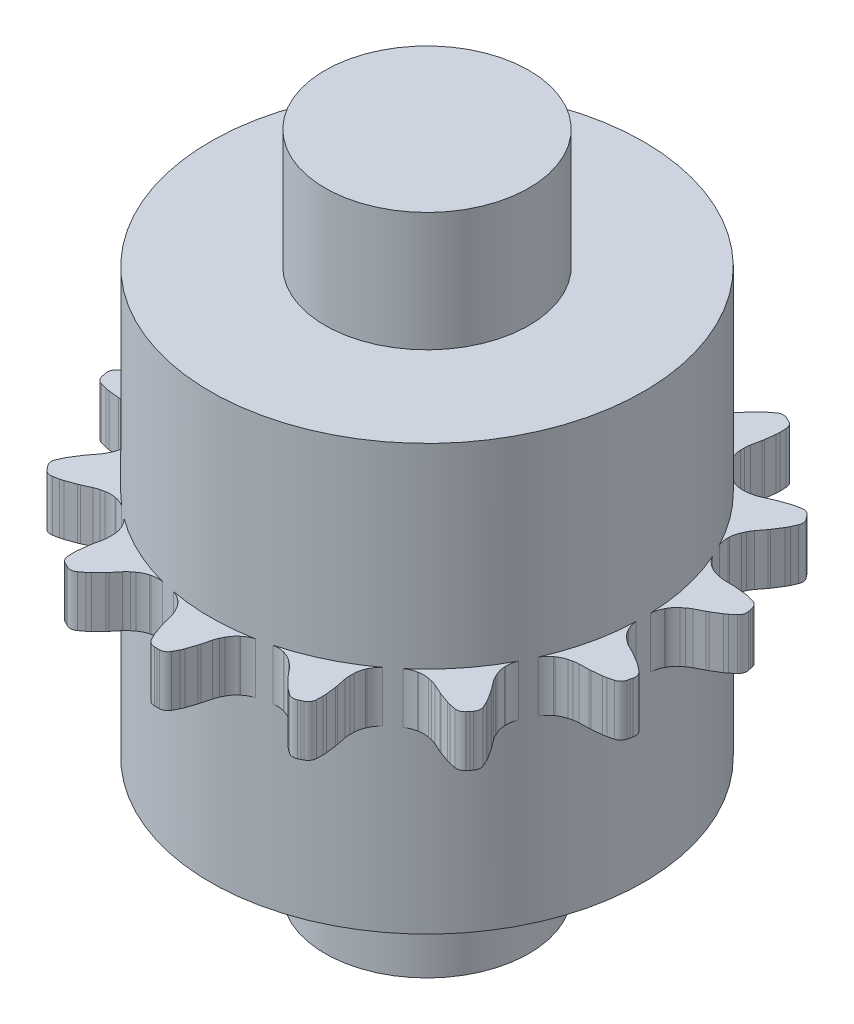
SolidWorks part; units mm, degrees
ref_plane "Front Plane" through (0, 0, 0) normal (0, 0, 1) x (1, 0, 0)
ref_plane "Top Plane" through (0, 0, 0) normal (0, 1, 0) x (1, 0, 0)
ref_plane "Right Plane" through (0, 0, 0) normal (1, 0, 0) x (0, 0, -1)
ref_axis "RotationAxis_J1_Radiator" through (0, 0, 0) along (0, 1, 0)
ref_plane "ContactPlane_J1_Bearing_Radiator" through (0, 0, 0) normal (0, 1, 0) x (1, 0, 0)
sketch "Sketch1" plane through (0, 0, 0) normal (0, 0, 1) x (1, 0, 0)
  line L0 (12.74, 25) -> (12.74, 0)
  line L1 (55, 0) -> (-55, 0) construction
  line L2 (12.74, 0) -> (6, 0)
  line L3 (6, 0) -> (6, -7)
  line L4 (6, -7) -> (0, -7)
  line L5 (0, -7) -> (0, 32)
  line L6 (0, 32) -> (6, 32)
  line L7 (6, 32) -> (6, 25)
  line L8 (6, 25) -> (12.74, 25)
  line L10 (0, 0) -> (0, 69.0457) construction
  point P14 (3, 32)
  dimension "D1" = 6
  dimension "D2" = 12.74
  dimension "D3" = 7
  dimension "D4" = 7
  dimension "D6" = 25
revolve "Revolve1" add sketch "Sketch1" angle 360 about axis through (0, 0, 0) along (0, 1, 0)
ref_plane "ContactPlane_J1_Radiator_Bearing" through (0, 25, 0) normal (0, 1, 0) x (1, 0, 0)
ref_plane "GearDefinitionPlane" through (0, 10.5, 0) normal (0, -1, 0) x (-1, 0, 0)
sketch "Sketch2" plane through (0, 10.5, 0) normal (0, -1, 0) x (-1, 0, 0)
sketch "Sketch3" plane through (0, 10.5, 0) normal (0, -1, 0) x (-1, 0, 0)
  line L0 (-2.86, 12.4148) -> (2.86, 12.4148)
  line L1 (0, 12.74) -> (0, 18.3584) construction
  line L2 (-2.86, 12.4148) -> (-2.5337, 12.4802)
  line L3 (-1.8465, 12.8171) -> (-1.7975, 12.8596)
  line L4 (-1.4378, 13.3226) -> (-1.333, 13.5324)
  line L5 (-1.2199, 13.8374) -> (-1.0814, 14.3883)
  line L6 (-1.0472, 14.5043) -> (-0.8487, 15.0895)
  line L7 (-0.7604, 15.2972) -> (-0.5938, 15.6191)
  line L8 (-0.1482, 15.8893) -> (0, 15.8888)
  line L9 (2.86, 12.4148) -> (2.5337, 12.4802)
  line L10 (1.8465, 12.8171) -> (1.7975, 12.8596)
  line L11 (0.1482, 15.8893) -> (0, 15.8888)
  line L12 (0.7604, 15.2972) -> (0.5938, 15.6191)
  line L13 (1.0472, 14.5043) -> (0.8487, 15.0895)
  line L14 (1.2199, 13.8374) -> (1.0814, 14.3883)
  line L15 (1.4378, 13.3226) -> (1.333, 13.5324)
  line L16 (2.8098, 12.4263) -> (3.1321, 12.3436)
  line L17 (3.8975, 12.349) -> (3.9601, 12.366)
  line L18 (4.485, 12.6271) -> (4.6705, 12.7706)
  line L19 (4.9047, 12.9964) -> (5.2686, 13.4326)
  line L20 (7.9634, 9.9445) -> (7.6978, 10.1449)
  line L21 (7.2248, 10.7466) -> (7.199, 10.8062)
  line L22 (7.0759, 11.3794) -> (7.0724, 11.6139)
  line L23 (7.1029, 11.9378) -> (7.2172, 12.4942)
  line L24 (7.2367, 12.6136) -> (7.3118, 13.2269)
  line L25 (7.3223, 13.4524) -> (7.3118, 13.8147)
  line L26 (7.0276, 14.2514) -> (6.8939, 14.3153)
  line L27 (6.7606, 14.38) -> (6.8939, 14.3153)
  line L28 (5.9521, 14.1122) -> (6.2419, 14.3299)
  line L29 (5.3497, 13.5223) -> (5.7824, 13.9634)
  line L30 (2.8098, 12.4263) -> (7.9634, 9.9445)
  line L31 (7.9231, 9.9766) -> (8.1777, 9.7623)
  line L32 (8.8695, 9.435) -> (8.9333, 9.4231)
  line L33 (9.5196, 9.4307) -> (9.7489, 9.4795)
  line L34 (10.0579, 9.5812) -> (10.575, 9.8164)
  line L35 (11.4895, 5.5045) -> (11.3372, 5.8003)
  line L36 (11.1721, 6.5477) -> (11.1747, 6.6125)
  line L37 (11.3125, 7.1824) -> (11.4111, 7.3951)
  line L38 (11.5791, 7.6737) -> (11.9235, 8.1255)
  line L39 (11.9929, 8.2246) -> (12.3266, 8.7446)
  line L40 (12.4339, 8.9432) -> (12.5817, 9.2741)
  line L41 (12.5151, 9.7909) -> (12.4224, 9.9065)
  line L42 (12.3303, 10.0227) -> (12.4224, 9.9065)
  line L43 (11.4858, 10.1321) -> (11.8413, 10.2026)
  line L44 (10.687, 9.862) -> (11.2683, 10.0717)
  line L45 (7.9231, 9.9766) -> (11.4895, 5.5045)
  line L46 (11.4672, 5.5509) -> (11.6035, 5.2473)
  line L47 (12.0849, 4.6523) -> (12.1372, 4.6139)
  line L48 (12.6687, 4.3664) -> (12.8965, 4.3108)
  line L49 (13.219, 4.2684) -> (13.7869, 4.256)
  line L50 (12.74, -0.0257) -> (12.7311, 0.3069)
  line L51 (12.9067, 1.0518) -> (12.9372, 1.1091)
  line L52 (13.3086, 1.5628) -> (13.4897, 1.7117)
  line L53 (13.7619, 1.8898) -> (14.2682, 2.1474)
  line L54 (14.3737, 2.2066) -> (14.9, 2.5303)
  line L55 (15.0829, 2.6626) -> (15.3596, 2.8967)
  line L56 (15.5239, 3.3912) -> (15.4904, 3.5356)
  line L57 (15.4579, 3.6802) -> (15.4904, 3.5356)
  line L58 (14.7445, 4.1453) -> (15.0954, 4.0545)
  line L59 (13.9076, 4.2485) -> (14.5223, 4.1852)
  line L60 (11.4672, 5.5509) -> (12.74, -0.0257)
  line L61 (12.74, 0.0257) -> (12.7311, -0.3069)
  line L62 (12.9067, -1.0518) -> (12.9372, -1.1091)
  line L63 (13.3086, -1.5628) -> (13.4897, -1.7117)
  line L64 (13.7619, -1.8898) -> (14.2682, -2.1474)
  line L65 (11.4672, -5.5509) -> (11.6035, -5.2473)
  line L66 (12.0849, -4.6523) -> (12.1372, -4.6139)
  line L67 (12.6687, -4.3664) -> (12.8965, -4.3108)
  line L68 (13.219, -4.2684) -> (13.7869, -4.256)
  line L69 (13.9076, -4.2485) -> (14.5223, -4.1852)
  line L70 (14.7445, -4.1453) -> (15.0954, -4.0545)
  line L71 (15.4579, -3.6802) -> (15.4904, -3.5356)
  line L72 (15.5239, -3.3912) -> (15.4904, -3.5356)
  line L73 (15.0829, -2.6626) -> (15.3596, -2.8967)
  line L74 (14.3737, -2.2066) -> (14.9, -2.5303)
  line L75 (12.74, 0.0257) -> (11.4672, -5.5509)
  line L76 (11.4895, -5.5045) -> (11.3372, -5.8003)
  line L77 (11.1721, -6.5477) -> (11.1747, -6.6125)
  line L78 (11.3125, -7.1824) -> (11.4111, -7.3951)
  line L79 (11.5791, -7.6737) -> (11.9235, -8.1255)
  line L80 (7.9231, -9.9766) -> (8.1777, -9.7623)
  line L81 (8.8695, -9.435) -> (8.9333, -9.4231)
  line L82 (9.5196, -9.4307) -> (9.7489, -9.4795)
  line L83 (10.0579, -9.5812) -> (10.575, -9.8164)
  line L84 (10.687, -9.862) -> (11.2683, -10.0717)
  line L85 (11.4858, -10.1321) -> (11.8413, -10.2026)
  line L86 (12.3303, -10.0227) -> (12.4224, -9.9065)
  line L87 (12.5151, -9.7909) -> (12.4224, -9.9065)
  line L88 (12.4339, -8.9432) -> (12.5817, -9.2741)
  line L89 (11.9929, -8.2246) -> (12.3266, -8.7446)
  line L90 (11.4895, -5.5045) -> (7.9231, -9.9766)
  line L91 (7.9634, -9.9445) -> (7.6978, -10.1449)
  line L92 (7.2248, -10.7466) -> (7.199, -10.8062)
  line L93 (7.0759, -11.3794) -> (7.0724, -11.6139)
  line L94 (7.1029, -11.9378) -> (7.2172, -12.4942)
  line L95 (2.8098, -12.4263) -> (3.1321, -12.3436)
  line L96 (3.8975, -12.349) -> (3.9601, -12.366)
  line L97 (4.485, -12.6271) -> (4.6705, -12.7706)
  line L98 (4.9047, -12.9964) -> (5.2686, -13.4326)
  line L99 (5.3497, -13.5223) -> (5.7824, -13.9634)
  line L100 (5.9521, -14.1122) -> (6.2419, -14.3299)
  line L101 (6.7606, -14.38) -> (6.8939, -14.3153)
  line L102 (7.0276, -14.2514) -> (6.8939, -14.3153)
  line L103 (7.3223, -13.4524) -> (7.3118, -13.8147)
  line L104 (7.2367, -12.6136) -> (7.3118, -13.2269)
  line L105 (7.9634, -9.9445) -> (2.8098, -12.4263)
  line L106 (2.86, -12.4148) -> (2.5337, -12.4802)
  line L107 (1.8465, -12.8171) -> (1.7975, -12.8596)
  line L108 (1.4378, -13.3226) -> (1.333, -13.5324)
  line L109 (1.2199, -13.8374) -> (1.0814, -14.3883)
  line L110 (-2.86, -12.4148) -> (-2.5337, -12.4802)
  line L111 (-1.8465, -12.8171) -> (-1.7975, -12.8596)
  line L112 (-1.4378, -13.3226) -> (-1.333, -13.5324)
  line L113 (-1.2199, -13.8374) -> (-1.0814, -14.3883)
  line L114 (-1.0472, -14.5043) -> (-0.8487, -15.0895)
  line L115 (-0.7604, -15.2972) -> (-0.5938, -15.6191)
  line L116 (-0.1482, -15.8893) -> (0, -15.8888)
  line L117 (0.1482, -15.8893) -> (0, -15.8888)
  line L118 (0.7604, -15.2972) -> (0.5938, -15.6191)
  line L119 (1.0472, -14.5043) -> (0.8487, -15.0895)
  line L120 (2.86, -12.4148) -> (-2.86, -12.4148)
  line L121 (-2.8098, -12.4263) -> (-3.1321, -12.3436)
  line L122 (-3.8975, -12.349) -> (-3.9601, -12.366)
  line L123 (-4.485, -12.6271) -> (-4.6705, -12.7706)
  line L124 (-4.9047, -12.9964) -> (-5.2686, -13.4326)
  line L125 (-7.9634, -9.9445) -> (-7.6978, -10.1449)
  line L126 (-7.2248, -10.7466) -> (-7.199, -10.8062)
  line L127 (-7.0759, -11.3794) -> (-7.0724, -11.6139)
  line L128 (-7.1029, -11.9378) -> (-7.2172, -12.4942)
  line L129 (-7.2367, -12.6136) -> (-7.3118, -13.2269)
  line L130 (-7.3223, -13.4524) -> (-7.3118, -13.8147)
  line L131 (-7.0276, -14.2514) -> (-6.8939, -14.3153)
  line L132 (-6.7606, -14.38) -> (-6.8939, -14.3153)
  line L133 (-5.9521, -14.1122) -> (-6.2419, -14.3299)
  line L134 (-5.3497, -13.5223) -> (-5.7824, -13.9634)
  line L135 (-2.8098, -12.4263) -> (-7.9634, -9.9445)
  line L136 (-7.9231, -9.9766) -> (-8.1777, -9.7623)
  line L137 (-8.8695, -9.435) -> (-8.9333, -9.4231)
  line L138 (-9.5196, -9.4307) -> (-9.7489, -9.4795)
  line L139 (-10.0579, -9.5812) -> (-10.575, -9.8164)
  line L140 (-11.4895, -5.5045) -> (-11.3372, -5.8003)
  line L141 (-11.1721, -6.5477) -> (-11.1747, -6.6125)
  line L142 (-11.3125, -7.1824) -> (-11.4111, -7.3951)
  line L143 (-11.5791, -7.6737) -> (-11.9235, -8.1255)
  line L144 (-11.9929, -8.2246) -> (-12.3266, -8.7446)
  line L145 (-12.4339, -8.9432) -> (-12.5817, -9.2741)
  line L146 (-12.5151, -9.7909) -> (-12.4224, -9.9065)
  line L147 (-12.3303, -10.0227) -> (-12.4224, -9.9065)
  line L148 (-11.4858, -10.1321) -> (-11.8413, -10.2026)
  line L149 (-10.687, -9.862) -> (-11.2683, -10.0717)
  line L150 (-7.9231, -9.9766) -> (-11.4895, -5.5045)
  line L151 (-11.4672, -5.5509) -> (-11.6035, -5.2473)
  line L152 (-12.0849, -4.6523) -> (-12.1372, -4.6139)
  line L153 (-12.6687, -4.3664) -> (-12.8965, -4.3108)
  line L154 (-13.219, -4.2684) -> (-13.7869, -4.256)
  line L155 (-12.74, 0.0257) -> (-12.7311, -0.3069)
  line L156 (-12.9067, -1.0518) -> (-12.9372, -1.1091)
  line L157 (-13.3086, -1.5628) -> (-13.4897, -1.7117)
  line L158 (-13.7619, -1.8898) -> (-14.2682, -2.1474)
  line L159 (-14.3737, -2.2066) -> (-14.9, -2.5303)
  line L160 (-15.0829, -2.6626) -> (-15.3596, -2.8967)
  line L161 (-15.5239, -3.3912) -> (-15.4904, -3.5356)
  line L162 (-15.4579, -3.6802) -> (-15.4904, -3.5356)
  line L163 (-14.7445, -4.1453) -> (-15.0954, -4.0545)
  line L164 (-13.9076, -4.2485) -> (-14.5223, -4.1852)
  line L165 (-11.4672, -5.5509) -> (-12.74, 0.0257)
  line L166 (-12.74, -0.0257) -> (-12.7311, 0.3069)
  line L167 (-12.9067, 1.0518) -> (-12.9372, 1.1091)
  line L168 (-13.3086, 1.5628) -> (-13.4897, 1.7117)
  line L169 (-13.7619, 1.8898) -> (-14.2682, 2.1474)
  line L170 (-11.4672, 5.5509) -> (-11.6035, 5.2473)
  line L171 (-12.0849, 4.6523) -> (-12.1372, 4.6139)
  line L172 (-12.6687, 4.3664) -> (-12.8965, 4.3108)
  line L173 (-13.219, 4.2684) -> (-13.7869, 4.256)
  line L174 (-13.9076, 4.2485) -> (-14.5223, 4.1852)
  line L175 (-14.7445, 4.1453) -> (-15.0954, 4.0545)
  line L176 (-15.4579, 3.6802) -> (-15.4904, 3.5356)
  line L177 (-15.5239, 3.3912) -> (-15.4904, 3.5356)
  line L178 (-15.0829, 2.6626) -> (-15.3596, 2.8967)
  line L179 (-14.3737, 2.2066) -> (-14.9, 2.5303)
  line L180 (-12.74, -0.0257) -> (-11.4672, 5.5509)
  line L181 (-11.4895, 5.5045) -> (-11.3372, 5.8003)
  line L182 (-11.1721, 6.5477) -> (-11.1747, 6.6125)
  line L183 (-11.3125, 7.1824) -> (-11.4111, 7.3951)
  line L184 (-11.5791, 7.6737) -> (-11.9235, 8.1255)
  line L185 (-7.9231, 9.9766) -> (-8.1777, 9.7623)
  line L186 (-8.8695, 9.435) -> (-8.9333, 9.4231)
  line L187 (-9.5196, 9.4307) -> (-9.7489, 9.4795)
  line L188 (-10.0579, 9.5812) -> (-10.575, 9.8164)
  line L189 (-10.687, 9.862) -> (-11.2683, 10.0717)
  line L190 (-11.4858, 10.1321) -> (-11.8413, 10.2026)
  line L191 (-12.3303, 10.0227) -> (-12.4224, 9.9065)
  line L192 (-12.5151, 9.7909) -> (-12.4224, 9.9065)
  line L193 (-12.4339, 8.9432) -> (-12.5817, 9.2741)
  line L194 (-11.9929, 8.2246) -> (-12.3266, 8.7446)
  line L195 (-11.4895, 5.5045) -> (-7.9231, 9.9766)
  line L196 (-7.9634, 9.9445) -> (-7.6978, 10.1449)
  line L197 (-7.2248, 10.7466) -> (-7.199, 10.8062)
  line L198 (-7.0759, 11.3794) -> (-7.0724, 11.6139)
  line L199 (-7.1029, 11.9378) -> (-7.2172, 12.4942)
  line L200 (-2.8098, 12.4263) -> (-3.1321, 12.3436)
  line L201 (-3.8975, 12.349) -> (-3.9601, 12.366)
  line L202 (-4.485, 12.6271) -> (-4.6705, 12.7706)
  line L203 (-4.9047, 12.9964) -> (-5.2686, 13.4326)
  line L204 (-5.3497, 13.5223) -> (-5.7824, 13.9634)
  line L205 (-5.9521, 14.1122) -> (-6.2419, 14.3299)
  line L206 (-6.7606, 14.38) -> (-6.8939, 14.3153)
  line L207 (-7.0276, 14.2514) -> (-6.8939, 14.3153)
  line L208 (-7.3223, 13.4524) -> (-7.3118, 13.8147)
  line L209 (-7.2367, 12.6136) -> (-7.3118, 13.2269)
  line L210 (-7.9634, 9.9445) -> (-2.8098, 12.4263)
  circle A0 centre (0, 0) radius 12.74 construction
  circle A1 centre (0, 0) radius 12.74
  arc A2 (-2.5337, 12.4802) -> (-1.8465, 12.8171) centre (-2.8285, 13.951) ccw
  arc A3 (-0.8487, 15.0895) -> (-0.7604, 15.2972) centre (0.5718, 14.6077) cw
  arc A4 (-1.0814, 14.3883) -> (-1.0472, 14.5043) centre (0.3733, 14.0226) cw
  arc A5 (-1.333, 13.5324) -> (-1.2199, 13.8374) centre (-2.6746, 14.2032) ccw
  arc A6 (-1.7975, 12.8596) -> (-1.4378, 13.3226) centre (-2.7795, 13.9935) ccw
  arc A7 (-0.5938, 15.6191) -> (-0.1482, 15.8893) centre (-0.1497, 15.3893) cw
  arc A8 (2.5337, 12.4802) -> (1.8465, 12.8171) centre (2.8285, 13.951) cw
  arc A9 (1.7975, 12.8596) -> (1.4378, 13.3226) centre (2.7795, 13.9935) cw
  arc A10 (0.5938, 15.6191) -> (0.1482, 15.8893) centre (0.1497, 15.3893) ccw
  arc A11 (1.333, 13.5324) -> (1.2199, 13.8374) centre (2.6746, 14.2032) cw
  arc A12 (1.0814, 14.3883) -> (1.0472, 14.5043) centre (-0.3733, 14.0226) ccw
  arc A13 (0.8487, 15.0895) -> (0.7604, 15.2972) centre (-0.5718, 14.6077) ccw
  arc A14 (3.1321, 12.3436) -> (3.8975, 12.349) centre (3.5047, 13.7967) ccw
  arc A15 (3.9601, 12.366) -> (4.485, 12.6271) centre (3.5673, 13.8136) ccw
  arc A16 (4.6705, 12.7706) -> (4.9047, 12.9964) centre (3.7528, 13.9571) ccw
  arc A17 (5.2686, 13.4326) -> (5.3497, 13.5223) centre (6.4205, 12.4719) cw
  arc A18 (7.6978, 10.1449) -> (7.2248, 10.7466) centre (8.6015, 11.3421) cw
  arc A19 (7.199, 10.8062) -> (7.0759, 11.3794) centre (8.5758, 11.4017) cw
  arc A20 (7.0724, 11.6139) -> (7.1029, 11.9378) centre (8.5723, 11.6361) cw
  arc A21 (7.2172, 12.4942) -> (7.2367, 12.6136) centre (5.7478, 12.7959) ccw
  arc A22 (7.3118, 13.2269) -> (7.3223, 13.4524) centre (5.8229, 13.4092) ccw
  arc A23 (7.3118, 13.8147) -> (7.0276, 14.2514) centre (6.8121, 13.8003) ccw
  arc A24 (6.2419, 14.3299) -> (6.7606, 14.38) centre (6.5422, 13.9302) cw
  arc A25 (5.7824, 13.9634) -> (5.9521, 14.1122) centre (6.8532, 12.913) cw
  arc A26 (8.1777, 9.7623) -> (8.8695, 9.435) centre (9.1437, 10.9097) ccw
  arc A27 (8.9333, 9.4231) -> (9.5196, 9.4307) centre (9.2076, 10.8979) ccw
  arc A28 (9.7489, 9.4795) -> (10.0579, 9.5812) centre (9.4369, 10.9466) ccw
  arc A29 (10.575, 9.8164) -> (10.687, 9.862) centre (11.1961, 8.451) cw
  arc A30 (11.3372, 5.8003) -> (11.1721, 6.5477) centre (12.6709, 6.4868) cw
  arc A31 (11.1747, 6.6125) -> (11.3125, 7.1824) centre (12.6735, 6.5517) cw
  arc A32 (11.4111, 7.3951) -> (11.5791, 7.6737) centre (12.7721, 6.7644) cw
  arc A33 (11.9235, 8.1255) -> (11.9929, 8.2246) centre (10.7305, 9.0348) ccw
  arc A34 (12.3266, 8.7446) -> (12.4339, 8.9432) centre (11.0643, 9.5548) ccw
  arc A35 (12.5817, 9.2741) -> (12.5151, 9.7909) centre (12.1252, 9.478) ccw
  arc A36 (11.8413, 10.2026) -> (12.3303, 10.0227) centre (11.9385, 9.7121) cw
  arc A37 (11.2683, 10.0717) -> (11.4858, 10.1321) centre (11.7773, 8.6607) cw
  arc A38 (11.6035, 5.2473) -> (12.0849, 4.6523) centre (12.9718, 5.862) ccw
  arc A39 (12.1372, 4.6139) -> (12.6687, 4.3664) centre (13.0241, 5.8236) ccw
  arc A40 (12.8965, 4.3108) -> (13.219, 4.2684) centre (13.2519, 5.7681) ccw
  arc A41 (13.7869, 4.256) -> (13.9076, 4.2485) centre (13.7541, 2.7563) cw
  arc A42 (12.7311, 0.3069) -> (12.9067, 1.0518) centre (14.2306, 0.3468) cw
  arc A43 (12.9372, 1.1091) -> (13.3086, 1.5628) centre (14.2611, 0.404) cw
  arc A44 (13.4897, 1.7117) -> (13.7619, 1.8898) centre (14.4422, 0.5529) cw
  arc A45 (14.2682, 2.1474) -> (14.3737, 2.2066) centre (13.5879, 3.4843) ccw
  arc A46 (14.9, 2.5303) -> (15.0829, 2.6626) centre (14.1143, 3.808) ccw
  arc A47 (15.3596, 2.8967) -> (15.5239, 3.3912) centre (15.0367, 3.2785) ccw
  arc A48 (15.0954, 4.0545) -> (15.4579, 3.6802) centre (14.9701, 3.5704) cw
  arc A49 (14.5223, 4.1852) -> (14.7445, 4.1453) centre (14.3687, 2.6931) cw
  arc A50 (12.7311, -0.3069) -> (12.9067, -1.0518) centre (14.2306, -0.3468) ccw
  arc A51 (12.9372, -1.1091) -> (13.3086, -1.5628) centre (14.2611, -0.404) ccw
  arc A52 (13.4897, -1.7117) -> (13.7619, -1.8898) centre (14.4422, -0.5529) ccw
  arc A53 (14.2682, -2.1474) -> (14.3737, -2.2066) centre (13.5879, -3.4843) cw
  arc A54 (11.6035, -5.2473) -> (12.0849, -4.6523) centre (12.9718, -5.862) cw
  arc A55 (12.1372, -4.6139) -> (12.6687, -4.3664) centre (13.0241, -5.8236) cw
  arc A56 (12.8965, -4.3108) -> (13.219, -4.2684) centre (13.2519, -5.7681) cw
  arc A57 (13.7869, -4.256) -> (13.9076, -4.2485) centre (13.7541, -2.7563) ccw
  arc A58 (14.5223, -4.1852) -> (14.7445, -4.1453) centre (14.3687, -2.6931) ccw
  arc A59 (15.0954, -4.0545) -> (15.4579, -3.6802) centre (14.9701, -3.5704) ccw
  arc A60 (15.3596, -2.8967) -> (15.5239, -3.3912) centre (15.0367, -3.2785) cw
  arc A61 (14.9, -2.5303) -> (15.0829, -2.6626) centre (14.1143, -3.808) cw
  arc A62 (11.3372, -5.8003) -> (11.1721, -6.5477) centre (12.6709, -6.4868) ccw
  arc A63 (11.1747, -6.6125) -> (11.3125, -7.1824) centre (12.6735, -6.5517) ccw
  arc A64 (11.4111, -7.3951) -> (11.5791, -7.6737) centre (12.7721, -6.7644) ccw
  arc A65 (11.9235, -8.1255) -> (11.9929, -8.2246) centre (10.7305, -9.0348) cw
  arc A66 (8.1777, -9.7623) -> (8.8695, -9.435) centre (9.1437, -10.9097) cw
  arc A67 (8.9333, -9.4231) -> (9.5196, -9.4307) centre (9.2076, -10.8979) cw
  arc A68 (9.7489, -9.4795) -> (10.0579, -9.5812) centre (9.4369, -10.9466) cw
  arc A69 (10.575, -9.8164) -> (10.687, -9.862) centre (11.1961, -8.451) ccw
  arc A70 (11.2683, -10.0717) -> (11.4858, -10.1321) centre (11.7773, -8.6607) ccw
  arc A71 (11.8413, -10.2026) -> (12.3303, -10.0227) centre (11.9385, -9.7121) ccw
  arc A72 (12.5817, -9.2741) -> (12.5151, -9.7909) centre (12.1252, -9.478) cw
  arc A73 (12.3266, -8.7446) -> (12.4339, -8.9432) centre (11.0643, -9.5548) cw
  arc A74 (7.6978, -10.1449) -> (7.2248, -10.7466) centre (8.6015, -11.3421) ccw
  arc A75 (7.199, -10.8062) -> (7.0759, -11.3794) centre (8.5758, -11.4017) ccw
  arc A76 (7.0724, -11.6139) -> (7.1029, -11.9378) centre (8.5723, -11.6361) ccw
  arc A77 (7.2172, -12.4942) -> (7.2367, -12.6136) centre (5.7478, -12.7959) cw
  arc A78 (3.1321, -12.3436) -> (3.8975, -12.349) centre (3.5047, -13.7967) cw
  arc A79 (3.9601, -12.366) -> (4.485, -12.6271) centre (3.5673, -13.8136) cw
  arc A80 (4.6705, -12.7706) -> (4.9047, -12.9964) centre (3.7528, -13.9571) cw
  arc A81 (5.2686, -13.4326) -> (5.3497, -13.5223) centre (6.4205, -12.4719) ccw
  arc A82 (5.7824, -13.9634) -> (5.9521, -14.1122) centre (6.8532, -12.913) ccw
  arc A83 (6.2419, -14.3299) -> (6.7606, -14.38) centre (6.5422, -13.9302) ccw
  arc A84 (7.3118, -13.8147) -> (7.0276, -14.2514) centre (6.8121, -13.8003) cw
  arc A85 (7.3118, -13.2269) -> (7.3223, -13.4524) centre (5.8229, -13.4092) cw
  arc A86 (2.5337, -12.4802) -> (1.8465, -12.8171) centre (2.8285, -13.951) ccw
  arc A87 (1.7975, -12.8596) -> (1.4378, -13.3226) centre (2.7795, -13.9935) ccw
  arc A88 (1.333, -13.5324) -> (1.2199, -13.8374) centre (2.6746, -14.2032) ccw
  arc A89 (1.0814, -14.3883) -> (1.0472, -14.5043) centre (-0.3733, -14.0226) cw
  arc A90 (-2.5337, -12.4802) -> (-1.8465, -12.8171) centre (-2.8285, -13.951) cw
  arc A91 (-1.7975, -12.8596) -> (-1.4378, -13.3226) centre (-2.7795, -13.9935) cw
  arc A92 (-1.333, -13.5324) -> (-1.2199, -13.8374) centre (-2.6746, -14.2032) cw
  arc A93 (-1.0814, -14.3883) -> (-1.0472, -14.5043) centre (0.3733, -14.0226) ccw
  arc A94 (-0.8487, -15.0895) -> (-0.7604, -15.2972) centre (0.5718, -14.6077) ccw
  arc A95 (-0.5938, -15.6191) -> (-0.1482, -15.8893) centre (-0.1497, -15.3893) ccw
  arc A96 (0.5938, -15.6191) -> (0.1482, -15.8893) centre (0.1497, -15.3893) cw
  arc A97 (0.8487, -15.0895) -> (0.7604, -15.2972) centre (-0.5718, -14.6077) cw
  arc A98 (-3.1321, -12.3436) -> (-3.8975, -12.349) centre (-3.5047, -13.7967) ccw
  arc A99 (-3.9601, -12.366) -> (-4.485, -12.6271) centre (-3.5673, -13.8136) ccw
  arc A100 (-4.6705, -12.7706) -> (-4.9047, -12.9964) centre (-3.7528, -13.9571) ccw
  arc A101 (-5.2686, -13.4326) -> (-5.3497, -13.5223) centre (-6.4205, -12.4719) cw
  arc A102 (-7.6978, -10.1449) -> (-7.2248, -10.7466) centre (-8.6015, -11.3421) cw
  arc A103 (-7.199, -10.8062) -> (-7.0759, -11.3794) centre (-8.5758, -11.4017) cw
  arc A104 (-7.0724, -11.6139) -> (-7.1029, -11.9378) centre (-8.5723, -11.6361) cw
  arc A105 (-7.2172, -12.4942) -> (-7.2367, -12.6136) centre (-5.7478, -12.7959) ccw
  arc A106 (-7.3118, -13.2269) -> (-7.3223, -13.4524) centre (-5.8229, -13.4092) ccw
  arc A107 (-7.3118, -13.8147) -> (-7.0276, -14.2514) centre (-6.8121, -13.8003) ccw
  arc A108 (-6.2419, -14.3299) -> (-6.7606, -14.38) centre (-6.5422, -13.9302) cw
  arc A109 (-5.7824, -13.9634) -> (-5.9521, -14.1122) centre (-6.8532, -12.913) cw
  arc A110 (-8.1777, -9.7623) -> (-8.8695, -9.435) centre (-9.1437, -10.9097) ccw
  arc A111 (-8.9333, -9.4231) -> (-9.5196, -9.4307) centre (-9.2076, -10.8979) ccw
  arc A112 (-9.7489, -9.4795) -> (-10.0579, -9.5812) centre (-9.4369, -10.9466) ccw
  arc A113 (-10.575, -9.8164) -> (-10.687, -9.862) centre (-11.1961, -8.451) cw
  arc A114 (-11.3372, -5.8003) -> (-11.1721, -6.5477) centre (-12.6709, -6.4868) cw
  arc A115 (-11.1747, -6.6125) -> (-11.3125, -7.1824) centre (-12.6735, -6.5517) cw
  arc A116 (-11.4111, -7.3951) -> (-11.5791, -7.6737) centre (-12.7721, -6.7644) cw
  arc A117 (-11.9235, -8.1255) -> (-11.9929, -8.2246) centre (-10.7305, -9.0348) ccw
  arc A118 (-12.3266, -8.7446) -> (-12.4339, -8.9432) centre (-11.0643, -9.5548) ccw
  arc A119 (-12.5817, -9.2741) -> (-12.5151, -9.7909) centre (-12.1252, -9.478) ccw
  arc A120 (-11.8413, -10.2026) -> (-12.3303, -10.0227) centre (-11.9385, -9.7121) cw
  arc A121 (-11.2683, -10.0717) -> (-11.4858, -10.1321) centre (-11.7773, -8.6607) cw
  arc A122 (-11.6035, -5.2473) -> (-12.0849, -4.6523) centre (-12.9718, -5.862) ccw
  arc A123 (-12.1372, -4.6139) -> (-12.6687, -4.3664) centre (-13.0241, -5.8236) ccw
  arc A124 (-12.8965, -4.3108) -> (-13.219, -4.2684) centre (-13.2519, -5.7681) ccw
  arc A125 (-13.7869, -4.256) -> (-13.9076, -4.2485) centre (-13.7541, -2.7563) cw
  arc A126 (-12.7311, -0.3069) -> (-12.9067, -1.0518) centre (-14.2306, -0.3468) cw
  arc A127 (-12.9372, -1.1091) -> (-13.3086, -1.5628) centre (-14.2611, -0.404) cw
  arc A128 (-13.4897, -1.7117) -> (-13.7619, -1.8898) centre (-14.4422, -0.5529) cw
  arc A129 (-14.2682, -2.1474) -> (-14.3737, -2.2066) centre (-13.5879, -3.4843) ccw
  arc A130 (-14.9, -2.5303) -> (-15.0829, -2.6626) centre (-14.1143, -3.808) ccw
  arc A131 (-15.3596, -2.8967) -> (-15.5239, -3.3912) centre (-15.0367, -3.2785) ccw
  arc A132 (-15.0954, -4.0545) -> (-15.4579, -3.6802) centre (-14.9701, -3.5704) cw
  arc A133 (-14.5223, -4.1852) -> (-14.7445, -4.1453) centre (-14.3687, -2.6931) cw
  arc A134 (-12.7311, 0.3069) -> (-12.9067, 1.0518) centre (-14.2306, 0.3468) ccw
  arc A135 (-12.9372, 1.1091) -> (-13.3086, 1.5628) centre (-14.2611, 0.404) ccw
  arc A136 (-13.4897, 1.7117) -> (-13.7619, 1.8898) centre (-14.4422, 0.5529) ccw
  arc A137 (-14.2682, 2.1474) -> (-14.3737, 2.2066) centre (-13.5879, 3.4843) cw
  arc A138 (-11.6035, 5.2473) -> (-12.0849, 4.6523) centre (-12.9718, 5.862) cw
  arc A139 (-12.1372, 4.6139) -> (-12.6687, 4.3664) centre (-13.0241, 5.8236) cw
  arc A140 (-12.8965, 4.3108) -> (-13.219, 4.2684) centre (-13.2519, 5.7681) cw
  arc A141 (-13.7869, 4.256) -> (-13.9076, 4.2485) centre (-13.7541, 2.7563) ccw
  arc A142 (-14.5223, 4.1852) -> (-14.7445, 4.1453) centre (-14.3687, 2.6931) ccw
  arc A143 (-15.0954, 4.0545) -> (-15.4579, 3.6802) centre (-14.9701, 3.5704) ccw
  arc A144 (-15.3596, 2.8967) -> (-15.5239, 3.3912) centre (-15.0367, 3.2785) cw
  arc A145 (-14.9, 2.5303) -> (-15.0829, 2.6626) centre (-14.1143, 3.808) cw
  arc A146 (-11.3372, 5.8003) -> (-11.1721, 6.5477) centre (-12.6709, 6.4868) ccw
  arc A147 (-11.1747, 6.6125) -> (-11.3125, 7.1824) centre (-12.6735, 6.5517) ccw
  arc A148 (-11.4111, 7.3951) -> (-11.5791, 7.6737) centre (-12.7721, 6.7644) ccw
  arc A149 (-11.9235, 8.1255) -> (-11.9929, 8.2246) centre (-10.7305, 9.0348) cw
  arc A150 (-8.1777, 9.7623) -> (-8.8695, 9.435) centre (-9.1437, 10.9097) cw
  arc A151 (-8.9333, 9.4231) -> (-9.5196, 9.4307) centre (-9.2076, 10.8979) cw
  arc A152 (-9.7489, 9.4795) -> (-10.0579, 9.5812) centre (-9.4369, 10.9466) cw
  arc A153 (-10.575, 9.8164) -> (-10.687, 9.862) centre (-11.1961, 8.451) ccw
  arc A154 (-11.2683, 10.0717) -> (-11.4858, 10.1321) centre (-11.7773, 8.6607) ccw
  arc A155 (-11.8413, 10.2026) -> (-12.3303, 10.0227) centre (-11.9385, 9.7121) ccw
  arc A156 (-12.5817, 9.2741) -> (-12.5151, 9.7909) centre (-12.1252, 9.478) cw
  arc A157 (-12.3266, 8.7446) -> (-12.4339, 8.9432) centre (-11.0643, 9.5548) cw
  arc A158 (-7.6978, 10.1449) -> (-7.2248, 10.7466) centre (-8.6015, 11.3421) ccw
  arc A159 (-7.199, 10.8062) -> (-7.0759, 11.3794) centre (-8.5758, 11.4017) ccw
  arc A160 (-7.0724, 11.6139) -> (-7.1029, 11.9378) centre (-8.5723, 11.6361) ccw
  arc A161 (-7.2172, 12.4942) -> (-7.2367, 12.6136) centre (-5.7478, 12.7959) cw
  arc A162 (-3.1321, 12.3436) -> (-3.8975, 12.349) centre (-3.5047, 13.7967) cw
  arc A163 (-3.9601, 12.366) -> (-4.485, 12.6271) centre (-3.5673, 13.8136) cw
  arc A164 (-4.6705, 12.7706) -> (-4.9047, 12.9964) centre (-3.7528, 13.9571) cw
  arc A165 (-5.2686, 13.4326) -> (-5.3497, 13.5223) centre (-6.4205, 12.4719) ccw
  arc A166 (-5.7824, 13.9634) -> (-5.9521, 14.1122) centre (-6.8532, 12.913) ccw
  arc A167 (-6.2419, 14.3299) -> (-6.7606, 14.38) centre (-6.5422, 13.9302) ccw
  arc A168 (-7.3118, 13.8147) -> (-7.0276, 14.2514) centre (-6.8121, 13.8003) cw
  arc A169 (-7.3118, 13.2269) -> (-7.3223, 13.4524) centre (-5.8229, 13.4092) cw
  point P20 (-2.1457, 12.558)
  dimension "D3" = 1.5
  dimension "D4" = 0.5
  dimension "D1" = 5.72
  dimension "D5" = 14
extrude "Boss-Extrude1" add sketch "Sketch3" against normal blind 3 contours A169 L209 A161 L199 A160 L198 A159 L197 A158 A1 A162 L201 A163 L202 A164 L203 A165 L204 A166 L205 A167 L206 L207 A168 L208 | A157 L194 A149 L184 A148 L183 A147 L182 A146 A1 A150 L186 A151 L187 A152 L188 A153 L189 A154 L190 A155 L191 L192 A156 L193 | A145 L179 A137 L169 A136 L168 A135 L167 A134 A1 A138 L171 A139 L172 A140 L173 A141 L174 A142 L175 A143 L176 L177 A144 L178 | A133 L164 A125 L154 A124 L153 A123 L152 A122 A1 A126 L156 A127 L157 A128 L158 A129 L159 A130 L160 A131 L161 L162 A132 L163 | A121 L149 A113 L139 A112 L138 A111 L137 A110 A1 A114 L141 A115 L142 A116 L143 A117 L144 A118 L145 A119 L146 L147 A120 L148 | A109 L134 A101 L124 A100 L123 A99 L122 A98 A1 A102 L126 A103 L127 A104 L128 A105 L129 A106 L130 A107 L131 L132 A108 L133 | A97 L119 A89 L109 A88 L108 A87 L107 A86 A1 A90 L111 A91 L112 A92 L113 A93 L114 A94 L115 A95 L116 L117 A96 L118 | A85 L104 A77 L94 A76 L93 A75 L92 A74 A1 A78 L96 A79 L97 A80 L98 A81 L99 A82 L100 A83 L101 L102 A84 L103 | A73 L89 A65 L79 A64 L78 A63 L77 A62 A1 A66 L81 A67 L82 A68 L83 A69 L84 A70 L85 A71 L86 L87 A72 L88 | A61 L74 A53 L64 A52 L63 A51 L62 A50 A1 A54 L66 A55 L67 A56 L68 A57 L69 A58 L70 A59 L71 L72 A60 L73 | A25 L29 A17 L19 A16 L18 A15 L17 A14 A1 A18 L21 A19 L22 A20 L23 A21 L24 A22 L25 A23 L26 L27 A24 L28 | A37 L44 A29 L34 A28 L33 A27 L32 A26 A1 A30 L36 A31 L37 A32 L38 A33 L39 A34 L40 A35 L41 L42 A36 L43 | A49 L59 A41 L49 A40 L48 A39 L47 A38 A1 A42 L51 A43 L52 A44 L53 A45 L54 A46 L55 A47 L56 L57 A48 L58 | L1 A1 A8 L10 A9 L15 A11 L14 A12 L13 A13 L12 A10 L11 | A1 L1 L8 A7 L7 A3 L6 A4 L5 A5 L4 A6 L3 A2 region at (6.062, 10.5, -12.5879) region at (0.644, 10.5, -13.9715) region at (-0.644, 10.5, -13.9715) region at (10.9233, 10.5, -8.7111) region at (-6.062, 10.5, -12.5879) region at (-10.9233, 10.5, -8.7111) region at (13.6212, 10.5, -3.1089) region at (-13.6212, 10.5, -3.1089) region at (13.6212, 10.5, 3.1089) region at (-13.6212, 10.5, 3.1089) region at (10.9233, 10.5, 8.7111) region at (-10.9233, 10.5, 8.7111) region at (6.062, 10.5, 12.5879) region at (-6.062, 10.5, 12.5879) region at (0, 10.5, 13.9715)
